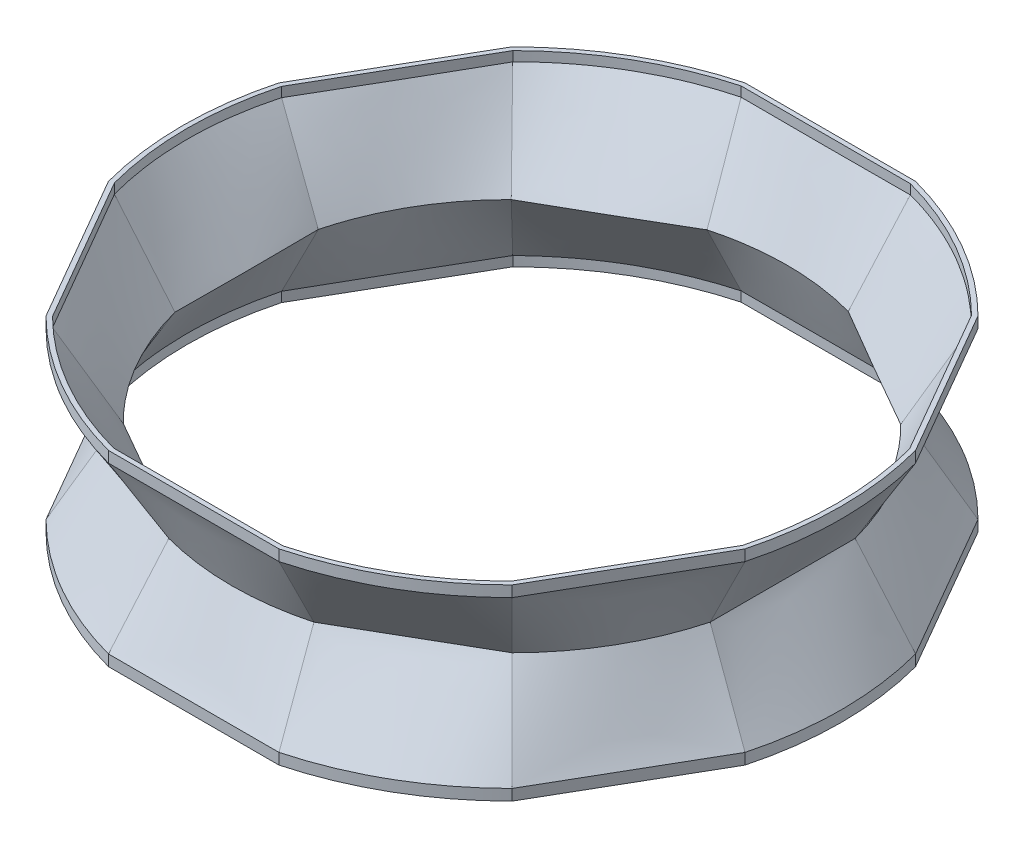
SolidWorks part; units mm, degrees
ref_plane "정면" through (0, 0, 0) normal (0, 0, 1) x (1, 0, 0)
ref_plane "윗면" through (0, 0, 0) normal (0, 1, 0) x (1, 0, 0)
ref_plane "우측면" through (0, 0, 0) normal (1, 0, 0) x (0, 0, -1)
sketch "스케치1" plane through (0, 0, 0) normal (0, 1, 0) x (1, 0, 0)
  line L1 (25.3808, -25.3808) -> (34.6708, -9.29)
  line L3 (34.6708, 9.29) -> (25.3808, 25.3808)
  line L5 (9.29, 34.6708) -> (-9.29, 34.6708)
  line L7 (-25.3808, 25.3808) -> (-34.6708, 9.29)
  line L9 (-34.6708, -9.29) -> (-25.3808, -25.3808)
  line L11 (-9.29, -34.6708) -> (9.29, -34.6708)
  line L13 (-9.29, 34.6708) -> (-17.3354, 30.0258) [skipped]
  line L14 (17.3354, 30.0258) -> (9.29, 34.6708) [skipped]
  line L15 (-34.6708, 0) -> (-34.6708, -9.29) [skipped]
  line L16 (-17.3354, -30.0258) -> (-9.29, -34.6708) [skipped]
  line L17 (9.29, -34.6708) -> (17.3354, -30.0258) [skipped]
  line L18 (34.6708, 0) -> (34.6708, 9.29) [skipped]
  circle A0 centre (0, 0) radius 34.6708 construction
  arc A1 (-9.29, 34.6708) -> (-25.3808, 25.3808) centre (0, 0) ccw
  arc A2 (25.3808, 25.3808) -> (9.29, 34.6708) centre (0, 0) ccw
  arc A3 (34.6708, -9.29) -> (34.6708, 9.29) centre (0, 0) ccw
  arc A4 (9.29, -34.6708) -> (25.3808, -25.3808) centre (0, 0) ccw
  arc A5 (-25.3808, -25.3808) -> (-9.29, -34.6708) centre (0, 0) ccw
  arc A6 (-34.6708, 9.29) -> (-34.6708, -9.29) centre (0, 0) ccw
  dimension "D1" = 18.58
extrude "보스-돌출1" add sketch "스케치1" along normal blind 1.2
ref_plane "평면1" through (0, 10.2, 0) normal (0, 1, 0) x (1, 0, 0)
sketch "스케치2" plane through (0, 10.2, 0) normal (0, 1, 0) x (1, 0, 0)
  line L1 (29.4832, -7.9) -> (29.4832, 7.9)
  line L3 (21.5832, 21.5832) -> (7.9, 29.4832)
  line L5 (-7.9, 29.4832) -> (-21.5832, 21.5832)
  line L7 (-29.4832, 7.9) -> (-29.4832, -7.9)
  line L9 (-21.5832, -21.5832) -> (-7.9, -29.4832)
  line L11 (7.9, -29.4832) -> (21.5832, -21.5832)
  line L13 (0, 29.4832) -> (-7.9, 29.4832) [skipped]
  line L14 (-25.5332, 14.7416) -> (-29.4832, 7.9) [skipped]
  line L15 (-25.5332, -14.7416) -> (-21.5832, -21.5832) [skipped]
  line L16 (0, -29.4832) -> (7.9, -29.4832) [skipped]
  line L17 (25.5332, -14.7416) -> (29.4832, -7.9) [skipped]
  line L18 (29.4832, 7.9) -> (25.5332, 14.7416) [skipped]
  circle A0 centre (0, 0) radius 29.4832 construction
  arc A1 (-21.5832, 21.5832) -> (-29.4832, 7.9) centre (0, 0) ccw
  arc A2 (-29.4832, -7.9) -> (-21.5832, -21.5832) centre (0, 0) ccw
  arc A3 (-7.9, -29.4832) -> (7.9, -29.4832) centre (0, 0) ccw
  arc A4 (21.5832, -21.5832) -> (29.4832, -7.9) centre (0, 0) ccw
  arc A5 (29.4832, 7.9) -> (21.5832, 21.5832) centre (0, 0) ccw
  arc A6 (7.9, 29.4832) -> (-7.9, 29.4832) centre (0, 0) ccw
  dimension "D1" = 15.8
sketch "스케치3" plane through (0, 1.2, 0) normal (0, 1, 0) x (1, 0, 0)
  line L13 (25.3808, -25.3808) -> (34.6708, -9.29)
  line L15 (34.6708, 9.29) -> (25.3808, 25.3808)
  line L17 (9.29, 34.6708) -> (-9.29, 34.6708)
  line L19 (-25.3808, 25.3808) -> (-34.6708, 9.29)
  line L21 (-34.6708, -9.29) -> (-25.3808, -25.3808)
  line L23 (-9.29, -34.6708) -> (9.29, -34.6708)
  line L25 (25.3808, -25.3808) -> (34.6708, -9.29)
  line L27 (34.6708, 9.29) -> (25.3808, 25.3808)
  line L29 (9.29, 34.6708) -> (-9.29, 34.6708)
  line L31 (-25.3808, 25.3808) -> (-34.6708, 9.29)
  line L33 (-34.6708, -9.29) -> (-25.3808, -25.3808)
  line L35 (-9.29, -34.6708) -> (9.29, -34.6708)
  arc A6 (9.29, -34.6708) -> (25.3808, -25.3808) centre (0, 0) ccw
  arc A7 (9.29, -34.6708) -> (25.3808, -25.3808) centre (0, 0) ccw
  arc A8 (34.6708, -9.29) -> (34.6708, 9.29) centre (0, 0) ccw
  arc A9 (34.6708, -9.29) -> (34.6708, 9.29) centre (0, 0) ccw
  arc A10 (25.3808, 25.3808) -> (9.29, 34.6708) centre (0, 0) ccw
  arc A11 (25.3808, 25.3808) -> (9.29, 34.6708) centre (0, 0) ccw
  arc A12 (-9.29, 34.6708) -> (-25.3808, 25.3808) centre (0, 0) ccw
  arc A13 (-9.29, 34.6708) -> (-25.3808, 25.3808) centre (0, 0) ccw
  arc A14 (-34.6708, 9.29) -> (-34.6708, -9.29) centre (0, 0) ccw
  arc A15 (-34.6708, 9.29) -> (-34.6708, -9.29) centre (0, 0) ccw
  arc A16 (-25.3808, -25.3808) -> (-9.29, -34.6708) centre (0, 0) ccw
  arc A17 (-25.3808, -25.3808) -> (-9.29, -34.6708) centre (0, 0) ccw
  dimension "D1" = 0
loft "로프트1" add profiles "스케치3", "스케치2" connector at (-25.3808, 1.2, -25.3808) connector at (-21.5832, 10.2, -21.5832)
mirror "대칭 복사1" about plane through (0, 10.2, 0) normal (0, 1, 0) of "보스-돌출1", "로프트1"
shell "쉘1" thickness 0.5 removed face at (0, 0, 0) removed face at (0, 20.4, 0)
